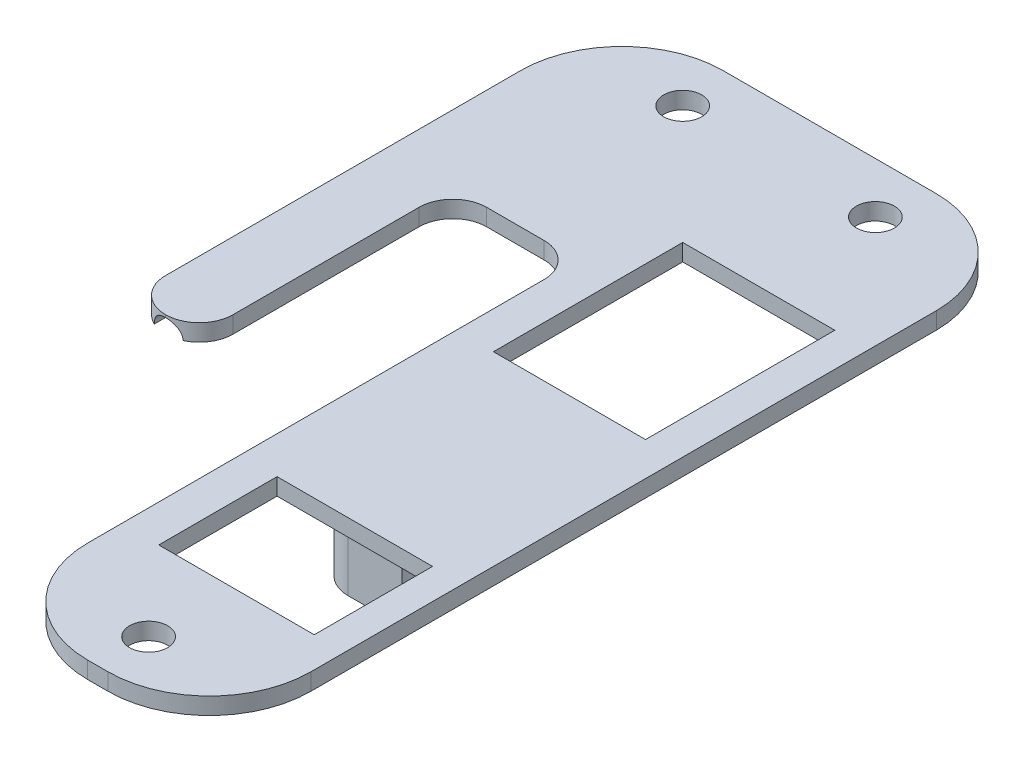
SolidWorks part; units mm, degrees
ref_plane "Front Plane" through (0, 0, 0) normal (0, 0, 1) x (1, 0, 0)
ref_plane "Top Plane" through (0, 0, 0) normal (0, 1, 0) x (1, 0, 0)
ref_plane "Right Plane" through (0, 0, 0) normal (1, 0, 0) x (0, 0, -1)
sketch "Sketch1" plane through (0, 0, 0) normal (0, 1, 0) x (1, 0, 0)
  line L0 (-16.6357, 24.6239) -> (7.9643, 24.6239)
  line L2 (-5.2357, 10.6239) -> (-5.2357, -24.3761)
  line L3 (-5.2357, -24.3761) -> (7.9643, -24.3761)
  line L4 (7.9643, 24.6239) -> (7.9643, -24.3761)
  line L7 (-5.2357, 10.6239) -> (-12.6357, 10.6239)
  line L9 (-16.6357, 24.6239) -> (-16.6357, -4.3761)
  line L12 (-16.6357, -4.3761) -> (-12.6357, -4.3761)
  line L13 (-12.6357, 10.6239) -> (-12.6357, -4.3761)
  dimension "D1" = 13.2
  dimension "D2" = 49
  dimension "D3" = 14
  dimension "D4" = 4
  dimension "D5" = 7.4
  dimension "D6" = 15
extrude "Boss-Extrude1" add sketch "Sketch1" along normal blind 1
sketch "Sketch4" plane through (0, 1, 0) normal (0, 1, 0) x (1, 0, 0)
  line L0 (7.9643, 24.6239) -> (-16.6357, 24.6239) construction
  line L1 (-16.6357, 24.6239) -> (-16.6357, -4.3761) construction
  line L3 (-5.2357, -24.3761) -> (7.9643, -24.3761) construction
  circle A0 centre (-10.0357, 21.6239) radius 1.125
  circle A1 centre (1.3643, 21.6239) radius 1.125
  circle A2 centre (1.3643, -21.3761) radius 1.125
  point P15 (1.3643, -24.3761)
  dimension "D1" = 2.25
  dimension "D2" = 2.25
  dimension "D3" = 2.25
  dimension "D4" = 3
  dimension "D5" = 3
  dimension "D6" = 6.6
  dimension "D8" = 3
extrude "Cut-Extrude3" cut sketch "Sketch4" against normal blind 6
sketch "Sketch3" plane through (0, 0, 4.3761) normal (0, 0, 1) x (1, 0, 0)
  line L1 (-16.6357, 0) -> (-12.6357, 0) construction
  circle A1 centre (-14.6357, 0) radius 0.85
  dimension "D1" = 1.7
fillet "Fillet1" radius 6 4 edges at (-5.2357, 0.5, 24.3761) (7.9643, 0.5, 24.3761) (7.9643, 0.5, -24.6239) (-16.6357, 0.5, -24.6239)
fillet "Fillet2" radius 2 4 edges at (-5.2357, 0.5, -10.6239) (-12.6357, 0.5, -10.6239) (-12.6357, 0.5, 4.3761) (-16.6357, 0.5, 4.3761)
extrude "Cut-Extrude5" cut sketch "Sketch3" against normal blind 20
sketch "Sketch6" plane through (0, 0, 0) normal (0, -1, 0) x (1, 0, 0)
  line L0 (-15.4857, -15.6239) -> (-15.4857, 4.1865) construction
  line L1 (-15.4857, -11.6239) -> (-4.4857, -11.6239)
  line L2 (-15.4857, -11.6239) -> (-15.4857, -18.6239)
  line L3 (-15.4857, -18.6239) -> (-4.4857, -18.6239)
  line L4 (-4.4857, -11.6239) -> (-4.4857, -18.6239)
  line L5 (-15.4857, -15.6239) -> (-13.7857, -15.6239) construction
  dimension "D1" = 7
  dimension "D2" = 3
  dimension "D3" = 11
extrude "Cut-Extrude6" cut sketch "Sketch6" against normal blind 0.7
sketch "Sketch7" plane through (0, 1, 0) normal (0, 1, 0) x (1, 0, 0)
  line L0 (0.7643, -24.3761) -> (1.9643, -24.3761) construction
  line L1 (-3.0357, -9.3761) -> (6.1643, -9.3761)
  line L2 (-3.0357, -9.3761) -> (-3.0357, -16.3761)
  line L3 (-3.0357, -16.3761) -> (6.1643, -16.3761)
  line L4 (6.1643, -9.3761) -> (6.1643, -16.3761)
  line L5 (7.9643, -18.3761) -> (7.9643, 18.6239) construction
  line L6 (-5.2357, 8.6239) -> (-5.2357, -18.3761) construction
  line L7 (1.9643, 24.6239) -> (-10.6357, 24.6239) construction
  line L8 (-3.0357, 14.6239) -> (5.9643, 14.6239)
  line L9 (-3.0357, 14.6239) -> (-3.0357, 3.4239)
  line L10 (-3.0357, 3.4239) -> (5.9643, 3.4239)
  line L11 (5.9643, 14.6239) -> (5.9643, 3.4239)
  dimension "D1" = 8
  dimension "D2" = 7
  dimension "D3" = 1.8
  dimension "D4" = 2.2
  dimension "D5" = 10
  dimension "D6" = 11.2
  dimension "D7" = 2
  dimension "D8" = 9
extrude "Cut-Extrude7" cut sketch "Sketch7" against normal through all
sketch "Sketch8" plane through (0, 0, 0) normal (0, -1, 0) x (1, 0, 0)
  line L0 (0.7643, 24.3761) -> (1.9643, 24.3761) construction
  line L1 (-2.8357, 7.3761) -> (2.3643, 7.3761)
  line L2 (-2.8357, 7.3761) -> (-2.8357, -2.6239)
  line L3 (-2.8357, -2.6239) -> (2.3643, -2.6239)
  line L4 (2.3643, 7.3761) -> (2.3643, -2.6239)
  line L5 (7.9643, 18.3761) -> (7.9643, -18.6239) construction
  line L6 (-5.2357, -8.6239) -> (-5.2357, 18.3761) construction
  dimension "D1" = 17
  dimension "D2" = 27
  dimension "D3" = 5.6
  dimension "D4" = 2.4
extrude "Boss-Extrude2" add sketch "Sketch8" along normal blind 5 contours L4 L3 L2 L1
fillet "Fillet4" radius 2 2 edges at (-2.8357, -2.5, -2.6239) (-2.8357, -2.5, 7.3761)
